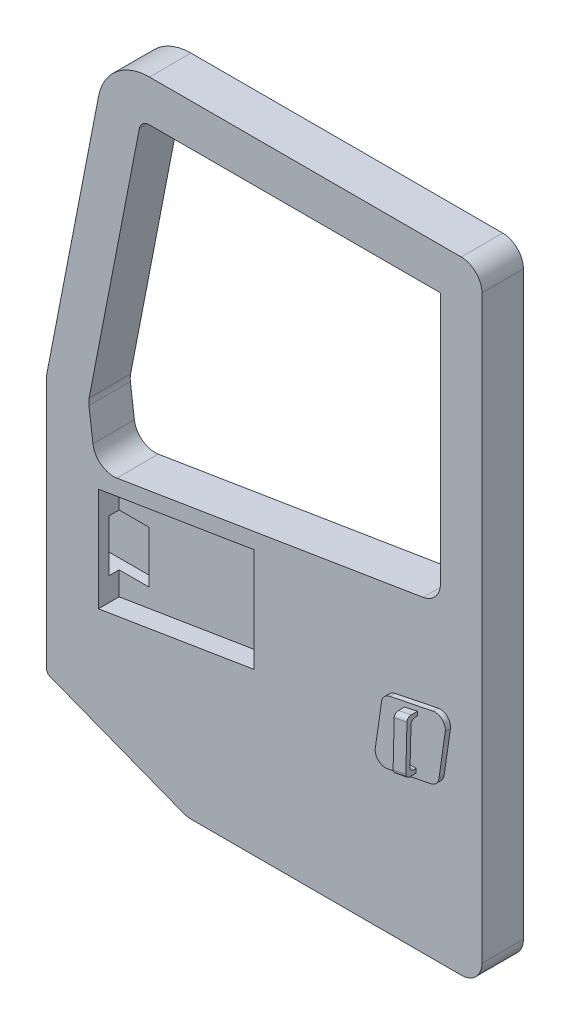
SolidWorks part; units mm, degrees
ref_plane "Front Plane" through (0, 0, 0) normal (0, 0, 1) x (1, 0, 0)
ref_plane "Top Plane" through (0, 0, 0) normal (0, 1, 0) x (1, 0, 0)
ref_plane "Right Plane" through (0, 0, 0) normal (1, 0, 0) x (0, 0, -1)
sketch "Sketch2" plane through (0, 0, 0) normal (0, 0, 1) x (1, 0, 0)
  line L0 (-405.8971, 659.2079) -> (-532.5433, 7.5919)
  line L1 (-179.7693, -762.022) -> (482.6, -762.022)
  line L3 (-281.2299, 761.978) -> (482.6, 761.978)
  line L4 (533.4, -711.222) -> (533.4, 711.178)
  line L5 (-459.8603, -656.939) -> (-452.0517, -645.784) construction
  line L6 (-417.9715, 597.0829) -> (44.1715, -63.1001) construction
  line L8 (-525.2852, -631.9868) -> (-198.1028, -758.5984)
  line L9 (-306.1633, 639.824) -> (-429.1581, 6.9955)
  line L10 (-429.6693, -9.2299) -> (-419.7789, -85.4932)
  line L14 (-281.2299, 660.378) -> (431.8, 660.378)
  line L15 (389.1621, -6.9365) -> (-361.2381, -129.0997)
  line L16 (431.7995, 43.2033) -> (431.8, 660.378)
  line L17 (431.8, -660.422) -> (431.8, 660.378) construction
  line L18 (-170.2829, -660.422) -> (431.8, -660.422) construction
  line L20 (-354.461, -589.1496) -> (-170.2829, -660.422) construction
  line L21 (-55.5325, -79.3316) -> (521.0599, 744.3665) construction
  line L22 (-306.1633, 639.824) -> (-430.7268, -1.0758) construction
  line L23 (-430.7268, -1.0758) -> (-354.461, -589.1496) construction
  line L24 (-416.9351, -673.9156) -> (-198.1028, -758.5984) construction
  line L25 (-179.7693, -762.022) -> (482.6, -762.022)
  line L27 (-281.2299, 761.978) -> (482.6, 761.978)
  line L28 (533.4, -711.222) -> (533.4, 711.178)
  line L29 (-459.8603, -656.939) -> (521.0599, 744.3665) construction
  line L30 (-417.9715, 597.0829) -> (521.0843, -744.3822) construction
  line L31 (-533.4018, 0.6529) -> (-448.7537, -652.0554) construction
  line L34 (-281.2299, 761.978) -> (482.6, 761.978)
  line L35 (-533.4018, 0.6529) -> (-533.4018, -620.1427)
  line L36 (-179.7693, -762.022) -> (482.6, -762.022)
  line L37 (533.4, 711.178) -> (533.4, -711.222)
  line L38 (-417.9715, 597.0829) -> (521.0843, -744.3822) construction
  line L39 (-460.0617, -657.2267) -> (521.0599, 744.3665) construction
  arc A0 (-405.8971, 659.2079) -> (-281.2299, 761.978) centre (-281.2299, 634.978) cw
  arc A2 (-532.5433, 7.5919) -> (-533.4018, 0.6529) centre (-482.6765, -2.1001) ccw
  arc A3 (533.4, 711.178) -> (482.6, 761.978) centre (482.6, 711.178) ccw
  arc A4 (482.6, -762.022) -> (533.4, -711.222) centre (482.6, -711.222) ccw
  arc A5 (-198.1028, -758.5984) -> (-179.7693, -762.022) centre (-179.7693, -711.222) ccw
  arc A7 (-354.461, -589.1496) -> (-354.461, -589.1496) centre (-354.461, -589.1496) ccw
  arc A8 (-170.2829, -660.422) -> (-170.2829, -660.422) centre (-170.2829, -660.422) ccw
  arc A9 (431.8, -660.422) -> (431.8, -660.422) centre (431.8, -660.422) ccw
  arc A10 (431.8, 660.378) -> (431.8, 660.378) centre (431.8, 660.378) ccw
  arc A11 (-306.1633, 639.824) -> (-281.2299, 660.378) centre (-281.2299, 634.978) cw
  arc A12 (-429.1581, 6.9955) -> (-429.6693, -9.2299) centre (-379.2912, -2.6964) ccw
  arc A13 (-430.7268, -1.0758) -> (-430.7268, -1.0758) centre (-430.7268, -1.0758) ccw construction
  arc A14 (431.7995, 43.2033) -> (389.1621, -6.9365) centre (380.9995, 43.2034) cw
  arc A15 (-419.7789, -85.4932) -> (-361.2381, -129.0997) centre (-369.4008, -78.9598) ccw
  arc A16 (-448.7537, -652.0554) -> (-416.9351, -673.9156) centre (-390.71, -601.6569) ccw construction
  arc A17 (-533.4018, -620.1427) -> (-525.2852, -631.9868) centre (-520.7018, -620.1427) ccw
  point P0 (0, 0)
  point P16 (-533.4, -0.0244)
  point P56 (0, 0)
  point P61 (0, 0)
  dimension "D3" = 127
  dimension "D5" = 50.8
  dimension "D6" = 50.8
  dimension "D8" = 50.8
  dimension "D2" = 12.7
  dimension "D1" = 1066.8
  dimension "D4" = 1524
  dimension "D7" = 101.6
extrude "Boss-Extrude1" add sketch "Sketch2" along normal mid plane 101.6 contours L8 A5 L1 A4 L4 A3 L3 A0 L0 A2 A15 L10 A12 L9 A11 L14 L16 A14 L15 region at (29.3865, -188.1823, 0)
sketch "Sketch3" plane through (0, 0, 50.8) normal (0, 0, 1) x (1, 0, 0)
  line L0 (320.1959, -245.101) -> (425.9265, -223.6716)
  line L3 (314.9201, -401.6691) -> (420.6507, -380.2397)
  line L4 (456.113, -252.1835) -> (440.7462, -358.9639)
  line L5 (300.1004, -266.3768) -> (284.7336, -373.1572)
  line L6 (310.4001, -194.8067) -> (287.3499, -354.9772) construction
  line L7 (-487.6326, -408.8312) -> (533.4008, -201.8888) construction
  line L8 (-457.3598, -558.1943) -> (563.6737, -351.2518) construction
  line L9 (461.2461, -216.515) -> (438.1959, -376.6855) construction
  line L10 (373.0612, -234.3863) -> (367.7854, -390.9544) construction
  line L11 (360.2667, -236.9795) -> (354.9908, -393.5476)
  line L12 (385.8558, -231.7931) -> (380.58, -388.3612)
  line L13 (360.3684, -233.9586) -> (355.0926, -390.5267) construction
  line L14 (385.754, -234.814) -> (380.4782, -391.3821) construction
  arc A0 (300.1004, -266.3768) -> (320.1959, -245.101) centre (325.2414, -269.9949) cw
  arc A1 (284.7336, -373.1572) -> (314.9201, -401.6691) centre (309.8746, -376.7752) ccw
  arc A2 (440.7462, -358.9639) -> (420.6507, -380.2397) centre (415.6052, -355.3458) cw
  arc A3 (456.113, -252.1835) -> (425.9265, -223.6716) centre (430.972, -248.5655) ccw
  dimension "D3" = 25.4
  dimension "D1" = 152.4
  dimension "D2" = 152.4
  dimension "D4" = 12.7
  dimension "D5" = 12.7
extrude "Boss-Extrude2" add sketch "Sketch3" along normal blind 12.7 contours L5 A1 L3 L11 L0 A0 | L4 A3 L0 L12 L3 A2 | L12 L0 L11 L3 region at (325.2101, -323.7797, 50.8) region at (370.4233, -312.6704, 50.8) region at (415.6365, -301.561, 50.8)
sketch "Sketch5" plane through (0, 0, 50.8) normal (0, 0, 1) x (1, 0, 0)
  line L0 (-429.6693, -9.2299) -> (-419.7789, -85.4932) construction
  line L1 (389.1621, -6.9365) -> (-361.2381, -129.0997) construction
  line L2 (431.7995, 43.2033) -> (431.8, 660.378) construction
  line L3 (-281.2299, 660.378) -> (431.8, 660.378) construction
  line L4 (-306.1633, 639.824) -> (-429.1581, 6.9955) construction
  line L5 (-429.6693, -9.2299) -> (-419.7789, -85.4932)
  line L6 (-179.7693, -762.022) -> (482.6, -762.022)
  line L12 (-179.7693, -762.022) -> (482.6, -762.022)
  line L18 (389.1621, -6.9365) -> (-361.2381, -129.0997)
  line L19 (431.7995, 43.2033) -> (431.8, 660.378)
  line L20 (-281.2299, 660.378) -> (431.8, 660.378)
  line L21 (-306.1633, 639.824) -> (-429.1581, 6.9955)
  line L28 (387.9598, -243.0291) -> (384.7172, -375.8602)
  line L29 (353.4927, -382.1888) -> (356.7353, -249.3577)
  line L30 (387.9598, -243.0291) -> (356.7353, -249.3577)
  line L31 (384.7172, -375.8602) -> (353.4927, -382.1888)
  line L32 (320.1959, -245.101) -> (425.9265, -223.6716) construction
  line L33 (314.9201, -401.6691) -> (420.6507, -380.2397) construction
  line L34 (320.1959, -245.101) -> (425.9265, -223.6716) construction
  line L35 (314.9201, -401.6691) -> (420.6507, -380.2397) construction
  arc A0 (-419.7789, -85.4932) -> (-361.2381, -129.0997) centre (-369.4008, -78.9598) ccw construction
  arc A1 (389.1621, -6.9365) -> (431.7995, 43.2033) centre (380.9995, 43.2034) ccw construction
  arc A2 (-281.2299, 660.378) -> (-306.1633, 639.824) centre (-281.2299, 634.978) ccw construction
  arc A3 (-429.1581, 6.9955) -> (-429.6693, -9.2299) centre (-379.2912, -2.6964) ccw construction
  arc A4 (-419.7789, -85.4932) -> (-361.2381, -129.0997) centre (-369.4008, -78.9598) ccw
  arc A5 (389.1621, -6.9365) -> (431.7995, 43.2033) centre (380.9995, 43.2034) ccw
  arc A18 (-281.2299, 660.378) -> (-306.1633, 639.824) centre (-281.2299, 634.978) ccw
  arc A19 (-429.1581, 6.9955) -> (-429.6693, -9.2299) centre (-379.2912, -2.6964) ccw
  dimension "D2" = 11.43
  dimension "D3" = 11.43
  dimension "D1" = 0
extrude "Boss-Extrude4" add sketch "Sketch5" along normal blind 38.1 contours L31 L28 L30 L29 region at (370.7262, -312.609, 50.8)
sketch "Sketch6" plane through (393.6581, -9.61, 0) normal (0.9997, -0.0244, 0) x (0, 0, -1)
  line L9 (-63.5, -356.1994) -> (-78.74, -356.1994)
  line L10 (-78.74, -356.1994) -> (-78.74, -243.6487)
  line L11 (-78.74, -243.6487) -> (-63.5, -243.6487)
  line L12 (-63.5, -356.1994) -> (-78.74, -356.1994)
  line L13 (-78.74, -356.1994) -> (-78.74, -243.6487)
  line L14 (-78.74, -243.6487) -> (-63.5, -243.6487)
  line M5 (-63.5, -366.3594) -> (-63.5, -233.4887)
  dimension "D1" = 10.16
extrude "Cut-Extrude6" cut sketch "Sketch6" against normal through all and the other way through all contours L14 L13 L12 M5 region at (386.3385, -309.4447, 71.12)
fillet "Fillet5" radius 10.16 4 edges at (369.1049, -379.0245, 88.9) (369.4394, -365.3242, 78.74) (372.1861, -252.8071, 78.74) (372.3476, -246.1934, 88.9)
sketch "Sketch7" plane through (-533.4018, 59.3738, 0) normal (1, 0, 0) x (0, 0, 1)
  line L0 (0, 821.3958) -> (0, -702.6042) construction
  line L1 (50.8, 821.3958) -> (-50.8, 821.3958) construction
  line L2 (50.8, -702.6042) -> (-50.8, -702.6042) construction
  line L3 (50.8, 58.7209) -> (-50.8, 58.7209) construction
  line L4 (-31.75, 84.1209) -> (31.75, 84.1209)
  line L5 (-31.75, 84.1209) -> (-31.75, 236.5209)
  line L6 (-31.75, 236.5209) -> (31.75, 236.5209)
  line L11 (31.75, 84.1209) -> (31.75, 236.5209)
  line L12 (-31.75, 84.1209) -> (31.75, 236.5209) construction
  line L13 (-31.75, 236.5209) -> (31.75, 84.1209) construction
  line L21 (-31.75, 642.9209) -> (31.75, 642.9209)
  line L28 (-31.75, 642.9209) -> (-31.75, 490.5209)
  line L29 (-31.75, 490.5209) -> (31.75, 490.5209)
  line L30 (31.75, 642.9209) -> (31.75, 490.5209)
  line L31 (-31.75, 642.9209) -> (31.75, 490.5209) construction
  line L32 (-31.75, 490.5209) -> (31.75, 642.9209) construction
  point P6 (0, 160.3209)
  point P13 (0, 566.7209)
  dimension "D1" = 63.5
  dimension "D2" = 152.4
  dimension "D3" = 25.4
  dimension "D4" = 254
extrude "Boss-Extrude5" add sketch "Sketch7" against normal blind 12.7
sketch "Sketch13" plane through (-546.1018, 0, 0) normal (-1, 0, 0) x (0, 0, 1)
  line L0 (0, -24.7471) -> (0, -177.1471) construction
  line L3 (-31.75, -24.7471) -> (31.75, -24.7471) construction
  line L6 (31.75, -177.1471) -> (-31.75, -177.1471) construction
  line L9 (31.75, -100.9471) -> (-31.75, -100.9471) construction
  line L10 (31.75, -24.7471) -> (31.75, -177.1471) construction
  line L11 (-31.75, -177.1471) -> (-31.75, -24.7471) construction
  line L12 (0, -431.1471) -> (0, -583.5471) construction
  line L13 (-31.75, -431.1471) -> (31.75, -431.1471) construction
  line L14 (31.75, -583.5471) -> (-31.75, -583.5471) construction
  line L15 (31.75, -507.3471) -> (-31.75, -507.3471) construction
  line L16 (31.75, -431.1471) -> (31.75, -583.5471) construction
  line L17 (-31.75, -583.5471) -> (-31.75, -431.1471) construction
  circle A4 centre (0, -50.1471) radius 11.43
  circle A6 centre (0, -151.7471) radius 11.43
  circle A7 centre (0, -456.5471) radius 11.43
  circle A8 centre (0, -558.1471) radius 11.43
  dimension "D1" = 50.8
  dimension "D2" = 22.86
  dimension "D3" = 50.8
  dimension "D4" = 22.86
extrude "Cut-Extrude7" cut sketch "Sketch13" against normal blind 46.99
sketch "Sketch14" plane through (-533.4018, 0, 0) normal (-1, 0, 0) x (0, 0, 1)
  line L0 (0, 761.978) -> (0, -758.5984) construction
  line L3 (50.8, 761.978) -> (-50.8, 761.978) construction
  line L4 (50.8, -758.5984) -> (-50.8, -758.5984) construction
  line L6 (-25.4, -371.7817) -> (25.4, -371.7817)
  line L7 (-25.4, -371.7817) -> (-25.4, -244.7817)
  line L8 (-25.4, -244.7817) -> (25.4, -244.7817)
  line L9 (25.4, -371.7817) -> (25.4, -244.7817)
  line L10 (-25.4, -371.7817) -> (25.4, -244.7817) construction
  line L11 (-25.4, -244.7817) -> (25.4, -371.7817) construction
  point P6 (0, -308.2817)
  dimension "D2" = 127
sketch "Sketch16" plane through (0, 0, 0) normal (0, 0, 1) x (1, 0, 0)
  line L0 (-406.4018, -175.0538) -> (-25.4018, -113.028)
  line L1 (-406.4018, -175.0538) -> (-406.4018, -429.0538)
  line L2 (-406.4018, -429.0538) -> (-25.4018, -367.028)
  line L3 (-25.4018, -367.028) -> (-25.4018, -113.028)
  line L4 (389.1621, -6.9365) -> (-361.2381, -129.0997) construction
  line L5 (-533.4018, 0.6529) -> (-533.4018, -620.1427) construction
  dimension "D1" = 381
  dimension "D2" = 254
  dimension "D3" = 38.1
  dimension "D4" = 127
extrude "Cut-Extrude8" cut sketch "Sketch16" along normal blind 379.73
extrude "Cut-Extrude9" cut sketch "Sketch14" against normal blind 200.406 contours L7 L8 L9 L6
equation "\"doorwidth\"= 42in"
equation "\"D1@Sketch2\"=\"doorwidth\""
equation "\"doorheight\"= 60in"
equation "\"D4@Sketch2\"=\"doorheight\""
equation "\"doorthickness\"= 4in"
equation "\"D1@Boss-Extrude1\"=\"doorthickness\""
equation "\"hingewidth\" = 2.5in"
equation "\"hingeheight\"= 6in"
equation "\"distanceofhinges\" = 10in"
equation "\"actuator slot width\"= 2in"
equation "\"actuator slot height\"= 5in"
equation "\"D2@Sketch14\"=\"actuator slot height\""
equation "\"D1@Sketch14\"=\"actuator slot width\""
equation "\"D1@Sketch7\"=\"hingewidth\""
equation "\"D2@Sketch7\"=\"hingeheight\""
equation "\"D4@Sketch7\"=\"distanceofhinges\""
